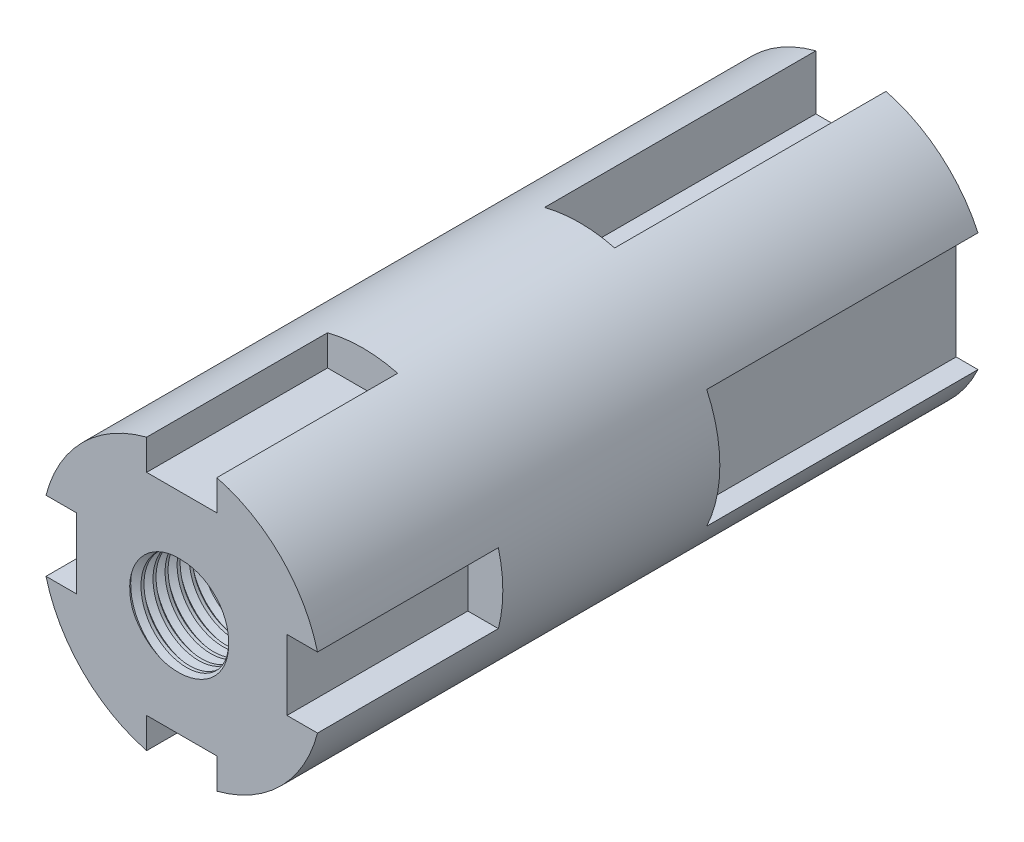
SolidWorks part; units mm, degrees
ref_plane "Front Plane" through (0, 0, 0) normal (0, 0, 1) x (1, 0, 0)
ref_plane "Top Plane" through (0, 0, 0) normal (0, 1, 0) x (1, 0, 0)
ref_plane "Right Plane" through (0, 0, 0) normal (1, 0, 0) x (0, 0, -1)
sketch "Sketch3" plane through (0, 0, 0) normal (0, 0, 1) x (1, 0, 0)
  circle A0 centre (0, 0) radius 5.815
  dimension "D1" = 11.63
extrude "Boss-Extrude2" add sketch "Sketch3" along normal blind 27.75
sketch "Sketch6" plane through (0, 0, 27.75) normal (0, 0, 1) x (1, 0, 0)
  line L10 (5.815, 1.455) -> (4.365, 1.455)
  line L11 (-1.455, 5.815) -> (1.455, 5.815)
  line L12 (-1.455, 5.815) -> (-1.455, 4.365)
  line L13 (-1.455, 4.365) -> (1.455, 4.365)
  line L14 (1.455, 5.815) -> (1.455, 4.365)
  line L15 (5.815, 1.455) -> (5.815, -1.455)
  line L16 (5.815, -1.455) -> (4.365, -1.455)
  line L17 (4.365, 1.455) -> (4.365, -1.455)
  line L18 (1.455, -5.815) -> (1.455, -4.365)
  line L19 (1.455, -5.815) -> (-1.455, -5.815)
  line L20 (-1.455, -5.815) -> (-1.455, -4.365)
  line L21 (1.455, -4.365) -> (-1.455, -4.365)
  line L22 (-5.815, -1.455) -> (-4.365, -1.455)
  line L23 (-5.815, -1.455) -> (-5.815, 1.455)
  line L24 (-5.815, 1.455) -> (-4.365, 1.455)
  line L25 (-4.365, -1.455) -> (-4.365, 1.455)
  circle A2 centre (0, 0) radius 5.815 construction
  point P4 (0, 5.815)
  point P23 (0, 0)
  dimension "D1" = 2.91
  dimension "D2" = 1.45
  dimension "D3" = 4
extrude "Cut-Extrude1" cut sketch "Sketch6" against normal blind 7.5
sketch "Sketch4" plane through (0, 0, 0) normal (0, 0, -1) x (-1, 0, 0)
  line L5 (-1.455, 3.365) -> (1.455, 3.365)
  line L6 (-1.455, 3.365) -> (-1.455, 5.815)
  line L7 (-1.455, 5.815) -> (1.455, 5.815)
  line L8 (1.455, 3.365) -> (1.455, 5.815)
  line L9 (-4.365, -2.455) -> (-5.815, -2.455)
  line L10 (-4.365, -2.455) -> (-4.365, 2.455)
  line L11 (-4.365, 2.455) -> (-5.815, 2.455)
  line L12 (-5.815, -2.455) -> (-5.815, 2.455)
  line L13 (-4.365, -2.455) -> (-5.815, 2.455) construction
  line L14 (-4.365, 2.455) -> (-5.815, -2.455) construction
  line L15 (4.365, -2.455) -> (5.815, -2.455)
  line L16 (4.365, -2.455) -> (4.365, 2.455)
  line L17 (4.365, 2.455) -> (5.815, 2.455)
  line L18 (5.815, -2.455) -> (5.815, 2.455)
  line L19 (4.365, -2.455) -> (5.815, 2.455) construction
  line L20 (4.365, 2.455) -> (5.815, -2.455) construction
  circle A2 centre (0, 0) radius 5.815 construction
  point P4 (0, 5.815)
  point P6 (-5.09, 0)
  point P13 (5.09, 0)
  dimension "D1" = 2.45
  dimension "D2" = 2.91
  dimension "D3" = 1.45
  dimension "D4" = 4.91
extrude "Cut-Extrude2" cut sketch "Sketch4" against normal blind 11.25
sketch "Sketch7" plane through (0, 0, 0) normal (0, 0, -1) x (-1, 0, 0)
  circle A0 centre (0, 0) radius 1.94
  dimension "D1" = 3.88
extrude "Cut-Extrude3" cut sketch "Sketch7" against normal blind 5
sketch "Sketch8" plane through (0, 0, 27.75) normal (0, 0, 1) x (1, 0, 0)
  circle A0 centre (0, 0) radius 1.94
  dimension "D1" = 3.88
extrude "Cut-Extrude4" cut sketch "Sketch8" against normal blind 5
thread "Thread1" pitch 0.5 method cut profile "Thread Profile1" start angle 0, offset 0, length 10, pitch 0.5, diameter 3.88
ref_plane "Plane1" through (-1.94, 0, 5) normal (0, -1, 0) x (-1, 0, 0)
sketch "Thread Profile1" plane through (-1.94, 0, 5) normal (0, -1, 0) x (-1, 0, 0)
  line L0 (0, 0) -> (0, 0.5) construction
  line L1 (0, 0) -> (0.2706, 0.1562)
  line L2 (0.2706, 0.1562) -> (0.2706, 0.2187)
  line L3 (0.2706, 0.2187) -> (0, 0.375)
  line L4 (0.2706, 0.1875) -> (0, 0.1875) construction
  line L11 (0, 0) -> (0, 0.375)
  point P2 (0, 0)
  dimension "Pitch" = 0.5
  dimension "Profile_Angle" = 60
  dimension "Profile_Land" = 0.0625
  dimension "Profile_Height" = 0.2706
thread "Thread2" pitch 0.5 method cut profile "Thread Profile2" start angle 0, offset 0, length 10, pitch 0.5, diameter 3.88
ref_plane "Plane2" through (1.94, 0, 22.75) normal (0, -1, 0) x (1, 0, 0)
sketch "Thread Profile2" plane through (1.94, 0, 22.75) normal (0, -1, 0) x (1, 0, 0)
  line L0 (0, 0) -> (0, 0.5) construction
  line L1 (0, 0) -> (0.2706, 0.1562)
  line L2 (0.2706, 0.1562) -> (0.2706, 0.2187)
  line L3 (0.2706, 0.2187) -> (0, 0.375)
  line L4 (0.2706, 0.1875) -> (0, 0.1875) construction
  line L11 (0, 0) -> (0, 0.375)
  point P2 (0, 0)
  dimension "Pitch" = 0.5
  dimension "Profile_Angle" = 60
  dimension "Profile_Land" = 0.0625
  dimension "Profile_Height" = 0.2706
equation "\"pin_diameter\"=11.63"
equation "\"pin_length\"=27.75"
equation "\"key_width\"=2.91"
equation "\"key_length\"=1.45"
equation "\"key_length_with_hump\"=2.45"
equation "\"key_width_with_offset\"=4.91"
equation "\"key_thickness\"=11.25"
equation "\"screw_diameter\"=3.88"
equation "\"D1@Sketch3\"=\"pin_diameter\""
equation "\"D1@Boss-Extrude2\"=\"pin_length\""
equation "\"D1@Sketch6\"=\"key_width\""
equation "\"D2@Sketch6\"=\"key_length\""
equation "\"D2@Sketch4\"=\"key_width\""
equation "\"D1@Sketch4\"=\"key_length_with_hump\""
equation "\"D4@Sketch4\"=\"key_width_with_offset\""
equation "\"D3@Sketch4\"=\"key_length\""
equation "\"D1@Cut-Extrude2\"=\"key_thickness\""
equation "\"D1@Sketch7\"=\"screw_diameter\""
equation "\"D1@Sketch8\"=\"screw_diameter\""
